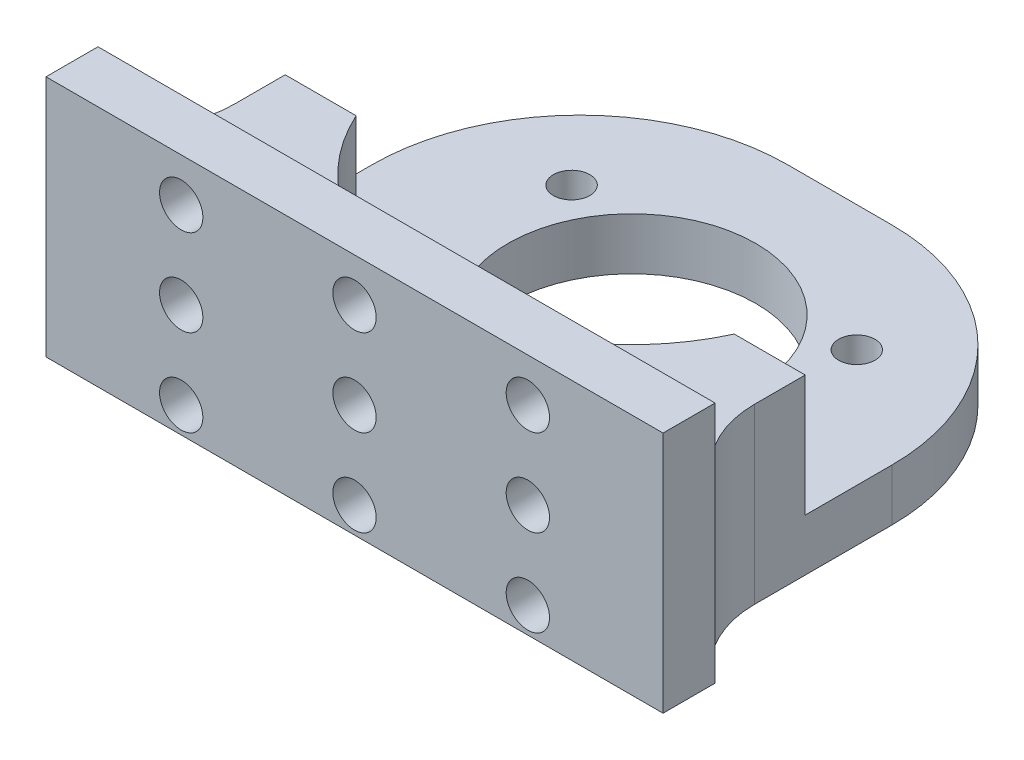
SolidWorks part; units mm, degrees
ref_plane "Front Plane" through (0, 0, 0) normal (0, 0, 1) x (1, 0, 0)
ref_plane "Top Plane" through (0, 0, 0) normal (0, 1, 0) x (1, 0, 0)
ref_plane "Right Plane" through (0, 0, 0) normal (1, 0, 0) x (0, 0, -1)
sketch "Sketch1" plane through (0, 0, 0) normal (0, 0, 1) x (1, 0, 0)
  line L1 (-15, -10) -> (15, -10)
  line L2 (-15, -10) -> (-15, 10)
  line L3 (-15, 10) -> (15, 10)
  line L4 (15, -10) -> (15, 10)
  line L5 (-15, -10) -> (15, 10) construction
  line L6 (-15, 10) -> (15, -10) construction
  point P0 (0, 0)
  point P11 (0, 0)
  point P13 (0, 0.5)
  dimension "D1" = 30
  dimension "D2" = 20
extrude "Main" add sketch "Sketch1" along normal blind 25
sketch "Sketch5" plane through (0, -10, 0) normal (0, -1, 0) x (-1, 0, 0)
  line L0 (0, -21.5) -> (-8.2272, -7.25) construction
  line L1 (-8.2272, -7.25) -> (8.2272, -7.25) construction
  line L2 (8.2272, -7.25) -> (0, -21.5) construction
  line L4 (15, 0) -> (-15, 0) construction
  circle A0 centre (0, -12) radius 9.5 construction
  circle A1 centre (0, -21.5) radius 1.05
  circle A2 centre (-8.2272, -7.25) radius 1.05
  circle A3 centre (8.2272, -7.25) radius 1.05
  circle A4 centre (0, -12) radius 7.15
  point P11 (0, 0)
  point P12 (0, -12.5)
  point P13 (0, 0)
  point P14 (0, -12.5)
  point P16 (-9.4545, -9.7951)
  point P17 (0, 0)
  point P18 (0, 0)
  dimension "D1" = 19
  dimension "D2" = 2.1
  dimension "D4" = 14.3
  dimension "D3" = 12
extrude "MainAndFixHole" cut sketch "Sketch5" against normal through all
sketch "Sketch6" plane through (0, -10, 0) normal (0, -1, 0) x (-1, 0, 0)
  circle A0 centre (0, -21.5) radius 2.2
  circle A1 centre (-8.2272, -7.25) radius 2.2
  circle A2 centre (8.2272, -7.25) radius 2.2
  dimension "D1" = 4.4
extrude "CoderFixHole2" cut sketch "Sketch6" against normal blind 1.5
sketch "Sketch7" plane through (15, 0, 0) normal (1, 0, 0) x (0, 0, -1)
  line L1 (-26, 10) -> (0, 10)
  line L2 (-26, 10) -> (-26, 0)
  line L3 (-26, 0) -> (0, 0)
  line L4 (0, 10) -> (0, 0)
  line L5 (-25, -10) -> (0, -10) construction
  line L7 (0, -10) -> (0, 10) construction
  point P4 (0, 10)
  point P6 (0, 10)
  point P9 (0, -7)
  dimension "D1" = 10
  dimension "D2" = 26
extrude "CoderHole" cut sketch "Sketch7" against normal through all
sketch "Sketch11" plane through (0, 0, 0) normal (0, 1, 0) x (1, 0, 0)
  line L0 (-15, 0) -> (15, 0)
  line L1 (15, 0) -> (15, -17)
  line L2 (15, -17) -> (10.9087, -17)
  line L3 (-15, 0) -> (-15, -17)
  line L4 (-15, -17) -> (-10.9087, -17)
  line L8 (-15, 0) -> (15, 0) construction
  line L9 (15, -25) -> (15, 0) construction
  arc A0 (10.9087, -17) -> (-10.9087, -17) centre (0, -12) cw
  circle A1 centre (0, -12) radius 7.15 construction
  point P3 (-10.7003, -12)
  point P8 (11, -12.6385)
  point P9 (-12, 0)
  point P11 (0, 0)
  point P12 (-11, -7.2042)
  point P14 (10.8949, -17.0301)
  point P17 (-10.8136, -17.2024)
  point P18 (-12, 0)
  point P19 (12, -16.3703)
  point P22 (12, -16.5463)
  point P23 (-13.0874, 0)
  point P25 (15, -12.1548)
  point P28 (15, 0)
  point P30 (11.2513, -16.1722)
  dimension "D1" = 12
  dimension "D2" = 5
extrude "CoderHole2" cut sketch "Sketch11" against normal blind 7
sketch "Sketch10" plane through (0, 0, 25) normal (0, 0, 1) x (1, 0, 0)
  line L0 (-15, -10) -> (15, -10) construction
  line L1 (-17.8, -10) -> (17.8, -10)
  line L2 (-17.8, -10) -> (-17.8, 4)
  line L3 (-17.8, 4) -> (17.8, 4)
  line L4 (17.8, -10) -> (17.8, 4)
  point P4 (0, -10)
  point P5 (0, -10)
  point P6 (0, 0)
  point P9 (0, -12.7416)
  dimension "D1" = 14
  dimension "D2" = 35.6
  dimension "D3" = 0
extrude "Link" add sketch "Sketch10" along normal blind 3
sketch "Sketch8" plane through (0, 0, 28) normal (0, 0, 1) x (1, 0, 0)
  line L0 (-10, 1.5) -> (10, 1.5) construction
  line L4 (-17.8, -10) -> (17.8, -10) construction
  line L5 (17.8, 4) -> (-17.8, 4) construction
  circle A0 centre (-10, 1.5) radius 1.25
  circle A1 centre (-10, -8.5) radius 1.25
  circle A2 centre (10, -8.5) radius 1.25
  circle A3 centre (10, 1.5) radius 1.25
  circle A4 centre (-10, -3.5) radius 1.25
  circle A5 centre (10, -3.5) radius 1.25
  circle A6 centre (0, 1.5) radius 1.25
  circle A7 centre (0, -8.5) radius 1.25
  circle A8 centre (0, -3.5) radius 1.25
  point P8 (0, 1.5)
  point P11 (0, 4)
  point P13 (0, 0)
  point P23 (0, 0)
  dimension "D3" = 2.5
  dimension "D5" = 2.5
  dimension "D7" = 2.5
  dimension "D1" = 20
  dimension "D2" = 10
  dimension "D4" = 1.5
  dimension "D6" = 5
extrude "VerticalHoles" cut sketch "Sketch8" against normal up to surface (3 mm away) up to face at (0, -4, 25)
fillet "Fillet4" radius 6 2 edges at (15, -5, 25) (-15, -5, 25)
fillet "Fillet6" radius 12 2 edges at (15, -8.5, 0) (-15, -8.5, 0)
